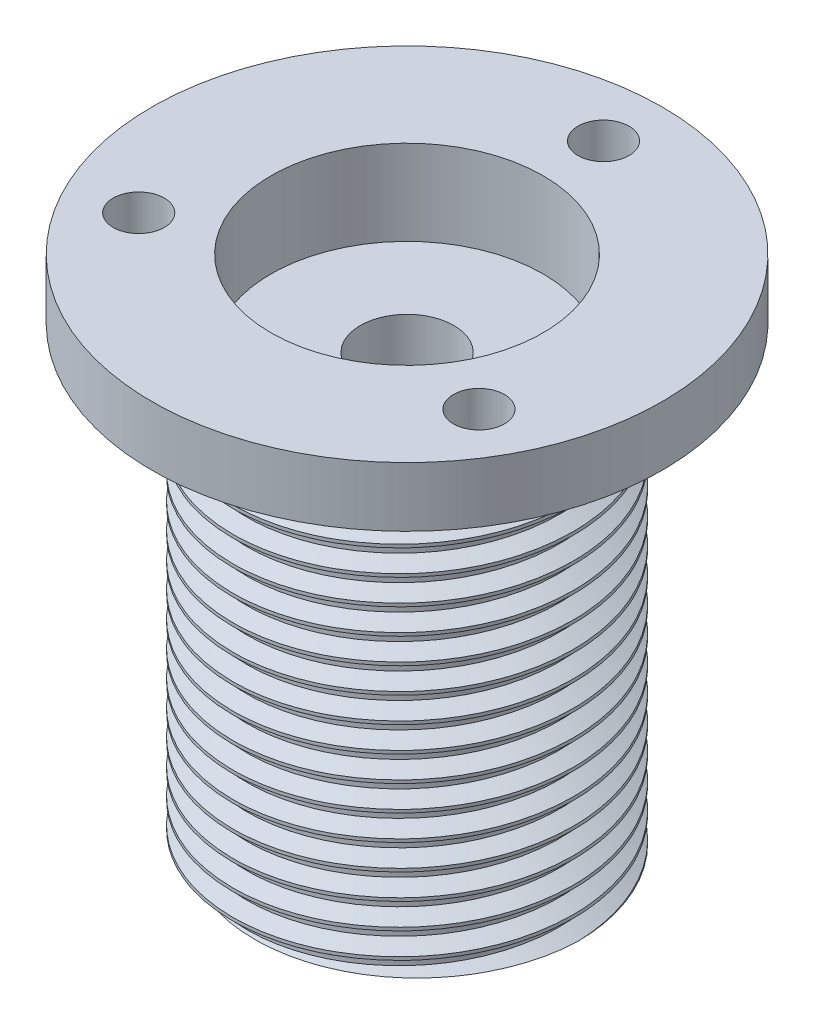
SolidWorks part; units mm, degrees
ref_plane "Front Plane" through (0, 0, 0) normal (0, 0, 1) x (1, 0, 0)
ref_plane "Top Plane" through (0, 0, 0) normal (0, 1, 0) x (1, 0, 0)
ref_plane "Right Plane" through (0, 0, 0) normal (1, 0, 0) x (0, 0, -1)
sketch "Sketch1" plane through (0, 0, 0) normal (1, 0, 0) x (0, 0, -1)
  line L2 (15, 30) -> (15, 26.5)
  line L3 (15, 26.5) -> (10, 26.5)
  line L4 (10, 23.825) -> (10, 0)
  line L6 (0, 0) -> (0, 30) construction
  line L7 (15, 30) -> (8, 30)
  line L8 (8, 30) -> (8, 25)
  line L9 (8, 25) -> (2.75, 25)
  line L10 (2.75, 25) -> (2.75, 5)
  line L11 (2.75, 5) -> (8, 5)
  line L12 (8, 5) -> (8, 0)
  line L13 (8, 0) -> (10, 0)
  line L14 (10, 26.5) -> (10, 23.825)
  dimension "D1" = 8
  dimension "D2" = 5.5
  dimension "D3" = 5
  dimension "D4" = 15
  dimension "D5" = 3.5
  dimension "D6" = 30
  dimension "D7" = 10
  dimension "D8" = 20
revolve "Revolve1" add sketch "Sketch1" angle 360 about L6
thread "Thread1" pitch 1.5 method cut profile "Thread Profile1" start angle 0, offset 3, length 26, pitch 1.5, diameter 20
ref_plane "Plane1" through (10, -3, 0) normal (0, 0, 1) x (1, 0, 0)
sketch "Thread Profile1" plane through (10, -3, 0) normal (0, 0, 1) x (1, 0, 0)
  line L0 (0, 0) -> (0, 1.5) construction
  line L11 (0, 0) -> (0, 1.3125)
  line L12 (0, 1.3125) -> (-0.8119, 0.8437)
  line L13 (-0.8119, 0.8437) -> (-0.8119, 0.4687)
  line L15 (-0.8119, 0.4687) -> (0, 0)
  line L17 (-0.8119, 0.6562) -> (0, 0.6562) construction
  point P2 (0, 0)
  dimension "Pitch" = 1.5
  dimension "Profile_Angle" = 60
  dimension "Profile_Land" = 0.375
  dimension "Profile_Height" = 0.8119
sketch "Sketch2" plane through (0, 30, 0) normal (0, 1, 0) x (1, 0, 0)
  line L1 (0, 11.547) -> (-10, -5.7735) construction
  line L2 (-10, -5.7735) -> (10, -5.7735) construction
  line L3 (10, -5.7735) -> (0, 11.547) construction
  circle A0 centre (0, 0) radius 5.7735 construction
  circle A1 centre (0, 11.547) radius 1.5
  circle A2 centre (10, -5.7735) radius 1.5
  circle A3 centre (-10, -5.7735) radius 1.5
  dimension "D2" = 3
  dimension "D1" = 20
extrude "Cut-Extrude1" cut sketch "Sketch2" against normal blind 4
